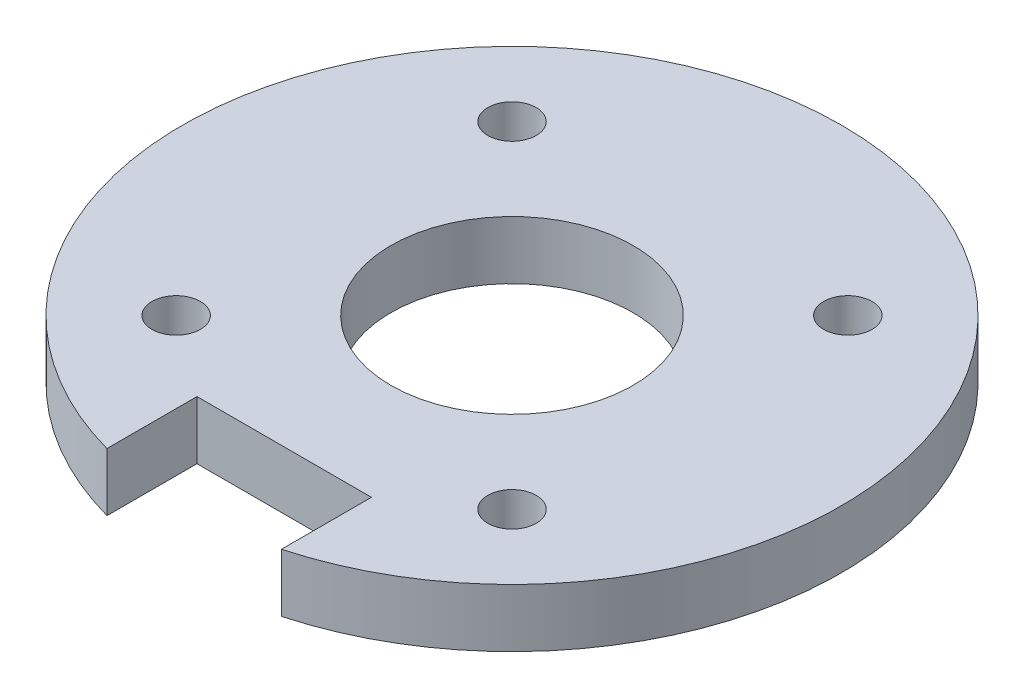
SolidWorks part; units mm, degrees
ref_plane "Front" through (0, 0, 0) normal (0, 0, 1) x (1, 0, 0)
ref_plane "Top" through (0, 0, 0) normal (0, 1, 0) x (1, 0, 0)
ref_plane "Right" through (0, 0, 0) normal (1, 0, 0) x (0, 0, -1)
sketch "Sketch1" plane through (0, 0, 0) normal (0, 1, 0) x (1, 0, 0)
  circle A0 centre (0, 0) radius 34
extrude "Boss-Extrude1" add sketch "Sketch1" along normal blind 6
hole_wizard "Hole1" positions "Sketch4" profile "Sketch3" legacy
sketch "Sketch4" plane through (0, 6, 0) normal (0, 1, 0) x (1, 0, 0)
  point P0 (17.324, 17.324)
sketch "Sketch3" plane through (17.324, 6, -17.324) normal (1, 0, 0) x (0, 0, 1)
  line L0 (0, 0) -> (0, 11.5022)
  line L1 (0, 11.5022) -> (2.5, 10)
  line L2 (2.5, 10) -> (2.5, 0)
  line L5 (2.5, 0) -> (0, 0)
  line L10 (0, 11.5022) -> (-2.5, 10) construction
  line L11 (0, -6.35) -> (0, 107.95) construction
  dimension "Hole Dia." = 5
  dimension "Hole Depth" = 10
  dimension "Drill Angle" = 118
ref_axis "Axis1" through (0, 50, 0) along (0, -1, 0)
pattern_circular "CirPattern1" count 4 over 360 about axis through (0, 50, 0) along (0, -1, 0) of "Hole1"
sketch "Sketch5" plane through (0, 6, 0) normal (0, 1, 0) x (1, 0, 0)
  circle A0 centre (0, 0) radius 12.5
extrude "Cut-Extrude1" cut sketch "Sketch5" against normal through all
sketch "Sketch7" plane through (0, 0, 0) normal (0, 1, 0) x (1, 0, 0)
  line L1 (-9, -80) -> (9, -80)
  line L2 (-9, -80) -> (-9, -23.5)
  line L3 (-9, -23.5) -> (9, -23.5)
  line L4 (9, -80) -> (9, -23.5)
  line L5 (-9, -80) -> (9, -23.5) construction
  line L6 (-9, -23.5) -> (9, -80) construction
  point P0 (0, -51.75)
extrude "Cut-Extrude4" cut sketch "Sketch7" along normal through all
